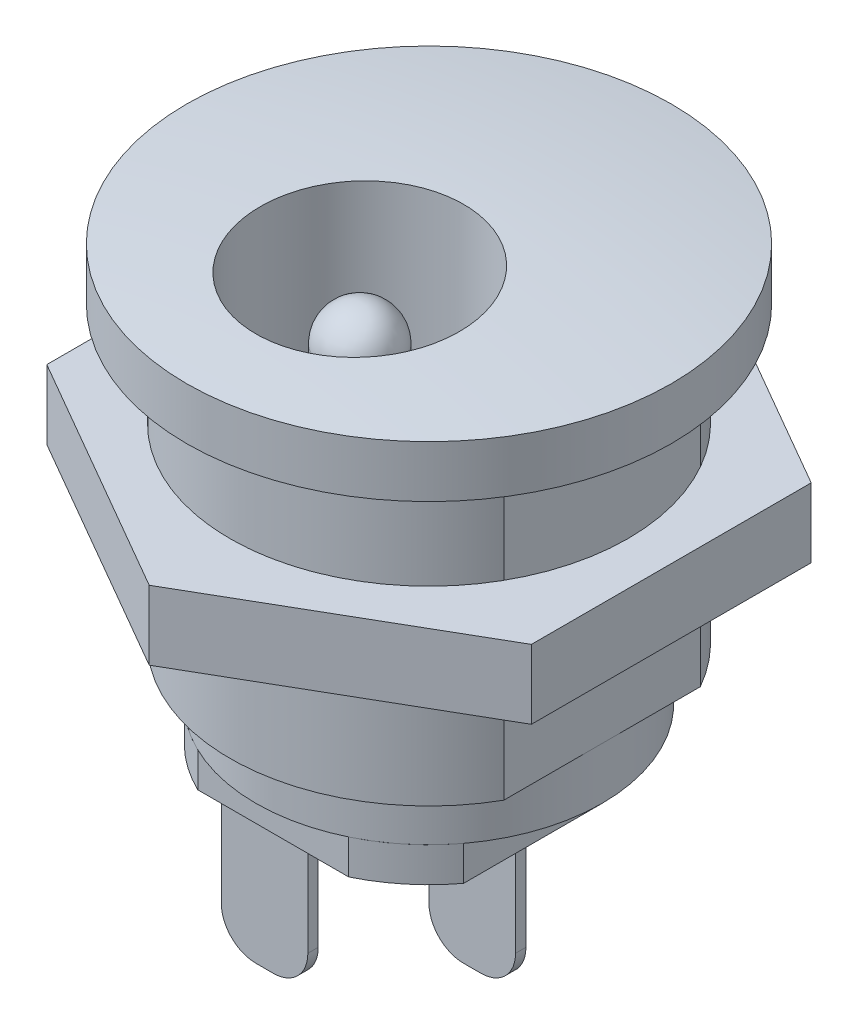
SolidWorks part; units mm, degrees
ref_plane "Front" through (0, 0, 0) normal (0, 0, 1) x (1, 0, 0)
ref_plane "Top" through (0, 0, 0) normal (0, 1, 0) x (1, 0, 0)
ref_plane "Right" through (0, 0, 0) normal (1, 0, 0) x (0, 0, -1)
sketch "Sketch1" plane through (0, 0, 0) normal (0, 1, 0) x (1, 0, 0)
  circle A0 centre (0, 0) radius 7
  dimension "D1" = 14
extrude "Boss-Extrude1" add sketch "Sketch1" along normal blind 1.5
dome "Dome1" faces to dome 1 distance 0.5 reverse direction no elliptical dome no face at (0, 1.5, 7) parameters "D1"=0.5
sketch "Sketch2" plane through (0, 0, 0) normal (0, -1, 0) x (1, 0, 0)
  circle A0 centre (0, 0) radius 5.75
  dimension "D1" = 11.5
extrude "Boss-Extrude2" add sketch "Sketch2" along normal blind 8.5
sketch "Sketch3" plane through (0, -8.5, 0) normal (0, -1, 0) x (1, 0, 0)
  circle A0 centre (0, 0) radius 5
  dimension "D1" = 10
extrude "Boss-Extrude3" add sketch "Sketch3" along normal blind 1.5
sketch "Sketch4" plane through (0, -8.5, 0) normal (0, -1, 0) x (1, 0, 0)
  line L0 (-5, 2.8395) -> (-5, -2.8395)
  line L1 (0, 0) -> (0, 7) construction
  line L2 (5, 2.8395) -> (5, -2.8395)
  circle A0 centre (0, 0) radius 5.75 construction
  arc A1 (-5, 2.8395) -> (-5, -2.8395) centre (0, 0) ccw
  circle A2 centre (0, 0) radius 5 construction
  circle A3 centre (0, 0) radius 7 construction
  arc A4 (5, 2.8395) -> (5, -2.8395) centre (0, 0) cw
extrude "Cut-Extrude1" cut sketch "Sketch4" against normal up to surface (8.5 mm away) up to face at (0, 0, -5.75)
sketch "Sketch5" plane through (0, -10, 0) normal (0, -1, 0) x (1, 0, 0)
  line L0 (-2.1794, 4.5) -> (2.1794, 4.5)
  line L1 (0, 4.5) -> (0, 0) construction
  line L2 (0, 0) -> (-5, 0) construction
  line L3 (-4, 3) -> (-4, -3)
  line L4 (4, 3) -> (4, -1)
  line L5 (-2.1794, -4.5) -> (2.1794, -4.5)
  line L6 (4, -1) -> (2.5, -1)
  line L7 (2.5, -1) -> (2.5, -4.3301)
  arc A2 (-4, -3) -> (-2.1794, -4.5) centre (0, 0) ccw
  arc A3 (-2.1794, 4.5) -> (-4, 3) centre (0, 0) ccw
  arc A4 (4, 3) -> (2.1794, 4.5) centre (0, 0) ccw
  arc A5 (5, 0) -> (-5, 0) centre (0, 0) ccw construction
  arc A8 (2.1794, -4.5) -> (2.5, -4.3301) centre (0, 0) ccw
  point P1 (0, 0)
  point P2 (4, 3)
  point P15 (-5, 0)
  dimension "D1" = 9
  dimension "D2" = 8
  dimension "D3" = 6.5
  dimension "D4" = 5.5
extrude "Boss-Extrude5" add sketch "Sketch5" along normal blind 1 separate body
sketch "Sketch6" plane through (0, 0, 0) normal (0, -1, 0) x (1, 0, 0)
  circle A0 centre (0, 2) radius 3
  circle A1 centre (0, 0) radius 7 construction
  point P2 (0, 0)
  dimension "D1" = 6
  dimension "D2" = 2
extrude "Cut-Extrude2" cut sketch "Sketch6" against normal through all and the other way blind 8
sketch "Sketch7" plane through (0, -8, 0) normal (0, 1, 0) x (1, 0, 0)
  circle A0 centre (0, -2) radius 1.05
  dimension "D1" = 2.1
extrude "Boss-Extrude6" add sketch "Sketch7" along normal blind 8
dome "Dome2" faces to dome 1 distance 1.05 reverse direction no elliptical dome no face at (0, 0, 3.05) parameters "D1"=1.05
sketch "Sketch8" plane through (0, 0, 0) normal (0, -1, 0) x (1, 0, 0)
  line L1 (7, -4.0415) -> (7, 4.0415)
  line L2 (7, 4.0415) -> (0, 8.0829)
  line L3 (0, 8.0829) -> (-7, 4.0415)
  line L4 (-7, 4.0415) -> (-7, -4.0415)
  line L5 (-7, -4.0415) -> (0, -8.0829)
  line L6 (0, -8.0829) -> (7, -4.0415)
  circle A0 centre (0, 0) radius 7 construction
  circle A1 centre (0, 0) radius 5.75
  dimension "D1" = 14
extrude "Boss-Extrude7" add sketch "Sketch8" along normal blind 2 from offset 3 separate body
sketch "Sketch9" plane through (0, -11, 0) normal (0, -1, 0) x (1, 0, 0)
  line L0 (-4, 3) -> (-4, -3) construction
  line L1 (-2.5, 3.5) -> (0, 3.5)
  line L2 (-2.5, 3.5) -> (-2.5, 3.2)
  line L3 (-2.5, 3.2) -> (0, 3.2)
  line L4 (0, 3.5) -> (0, 3.2)
  line L5 (0.5, 0.5) -> (3, 0.5)
  line L6 (0.5, 0.5) -> (0.5, 0.2)
  line L7 (0.5, 0.2) -> (3, 0.2)
  line L8 (3, 0.5) -> (3, 0.2)
  line L9 (-3.5, -0.5) -> (-3.2, -0.5)
  line L10 (-3.5, -0.5) -> (-3.5, -3)
  line L11 (-3.5, -3) -> (-3.2, -3)
  line L12 (-3.2, -0.5) -> (-3.2, -3)
  line L13 (2.1794, 4.5) -> (-2.1794, 4.5) construction
  line L14 (4, -1) -> (4, 3) construction
  line L15 (-2.1794, -4.5) -> (2.1794, -4.5) construction
  dimension "D1" = 0.3
  dimension "D2" = 2.5
  dimension "D3" = 0.5
  dimension "D4" = 1
  dimension "D5" = 1
  dimension "D6" = 4
  dimension "D7" = 1.5
  dimension "D8" = 1.5
extrude "Boss-Extrude8" add sketch "Sketch9" along normal blind 4.5
fillet "Fillet1" radius 1 6 edges at (-3.35, -15.5, -3) (-3.35, -15.5, -0.5) (3, -15.5, 0.35) (0.5, -15.5, 0.35) (0, -15.5, 3.35) (-2.5, -15.5, 3.35)
